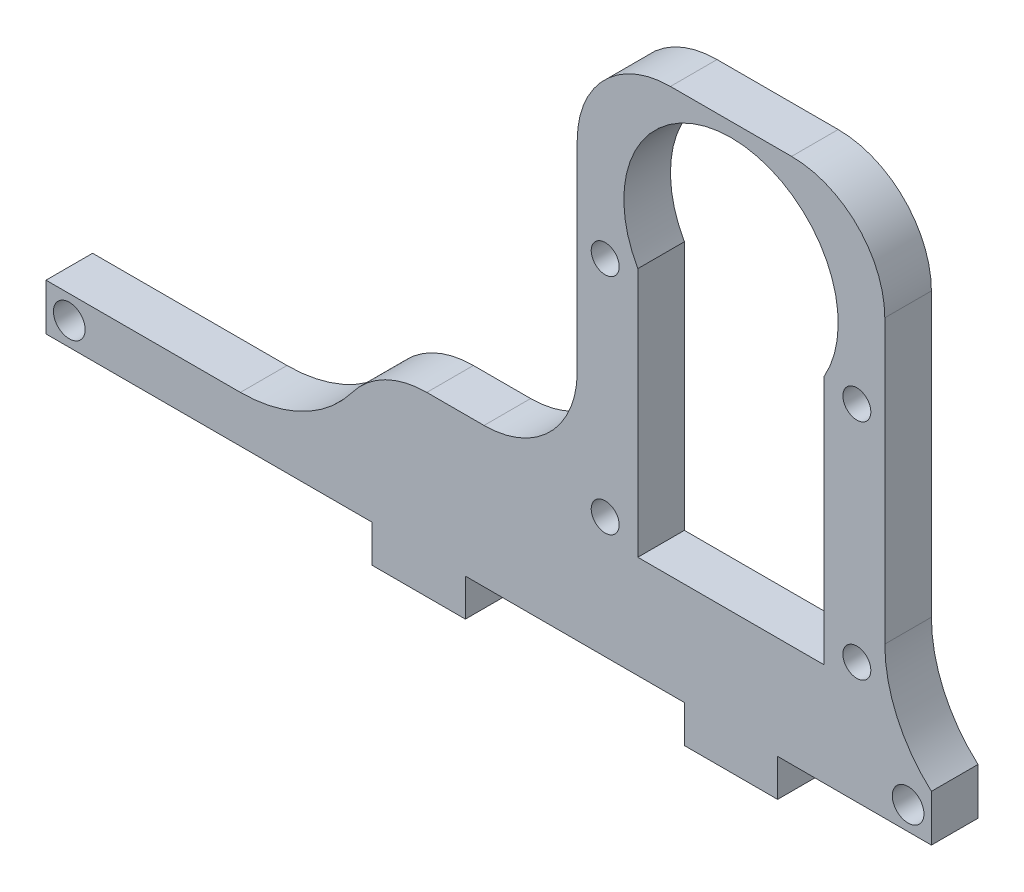
SolidWorks part; units mm, degrees
note: The reader was unsure of these and kept them because the rebuilt part matched: thickness of "Base-Flange1", "Sheet-Metal1".
ref_plane "Front Plane" through (0, 0, 0) normal (0, 0, 1) x (1, 0, 0)
ref_plane "Top Plane" through (0, 0, 0) normal (0, 1, 0) x (1, 0, 0)
ref_plane "Right Plane" through (0, 0, 0) normal (1, 0, 0) x (0, 0, -1)
sketch "Sketch2" plane through (0, 0, 0) normal (0, 0, 1) x (1, 0, 0)
  line L0 (-13.5, -30.5) -> (-13.5, -6.5) construction
  line L1 (-6.5, 13) -> (6.5, 13)
  line L3 (-28.5, -43.5) -> (-5, -43.5)
  line L4 (16.5, 3) -> (16.5, -38.5)
  line L5 (-10, -5.6789) -> (10, -5.6789) construction
  line L6 (-38.5, -43.5) -> (-28.5, -43.5) construction
  line L7 (-38.5, -43.5) -> (-28.5, -43.5) construction
  line L8 (-38.5, -43.5) -> (-38.5, -47.5)
  line L9 (-38.5, -47.5) -> (-28.5, -47.5)
  line L10 (-28.5, -43.5) -> (-28.5, -47.5)
  line L14 (-5, -43.5) -> (-5, -47.5)
  line L16 (-10, -5.6789) -> (-10, -32.5)
  line L21 (-10, -32.5) -> (10, -32.5)
  line L22 (10, -5.6789) -> (10, -32.5)
  line L23 (-13.5, -6.5) -> (13.5, -6.5) construction
  line L24 (-16.5, 3) -> (-16.5, -28.5)
  line L25 (-16.5, -28.5) -> (-38.5, -28.5)
  line L26 (-38.5, -28.5) -> (-38.5, -38.5)
  line L27 (-5, -47.5) -> (5, -47.5)
  line L28 (5, -43.5) -> (16.5, -43.5)
  line L29 (5, -47.5) -> (5, -43.5)
  line L30 (16.5, -38.5) -> (16.5, -43.5) construction
  line L31 (16.5, -43.5) -> (21.5, -43.5)
  line L32 (16.5, -43.5) -> (16.5, -38.5) construction
  line L33 (16.5, -38.5) -> (21.5, -38.5)
  line L34 (21.5, -43.5) -> (21.5, -38.5)
  line L35 (-38.5, -38.5) -> (-38.5, -43.5) construction
  line L36 (-38.5, -43.5) -> (-73.5, -43.5)
  line L37 (-38.5, -43.5) -> (-38.5, -38.5) construction
  line L38 (-38.5, -38.5) -> (-73.5, -38.5)
  line L39 (-73.5, -43.5) -> (-73.5, -38.5)
  arc A6 (6.5, 13) -> (16.5, 3) centre (6.5, 3) cw
  arc A7 (-6.5, 13) -> (-16.5, 3) centre (-6.5, 3) ccw
  arc A12 (10, -5.6789) -> (-10, -5.6789) centre (0, 0) ccw
  circle A13 centre (-13.5, -6.5) radius 1.5
  circle A14 centre (-13.5, -30.5) radius 1.5
  circle A15 centre (13.5, -6.5) radius 1.5
  circle A16 centre (13.5, -30.5) radius 1.5
  arc A17 (-10, -5.6789) -> (-9.4868, -6.5) centre (0, 0) ccw construction
  arc A18 (-9.4868, -6.5) -> (9.4868, -6.5) centre (0, 0) ccw construction
  arc A19 (9.4868, -6.5) -> (10, -5.6789) centre (0, 0) ccw construction
  circle A20 centre (19, -41) radius 1.7
  circle A21 centre (-71, -41) radius 1.7
  point P29 (0, -6.5)
  point P31 (0, 13)
  point P32 (0, -32.5)
  point P35 (0, -47.5)
  point P43 (21.5, -41)
  point P45 (19, -43.5)
  point P50 (-73.5, -41)
  dimension "D2" = 23
  dimension "D3" = 32.5
  dimension "D4" = 20
  dimension "D12" = 10
  dimension "D13" = 10
  dimension "D18" = 5
  dimension "D6" = 3
  dimension "D11" = 13
  dimension "D20" = 3.4
  dimension "D23" = 3.4
  dimension "D5" = 43.5
  dimension "D7" = 27
  dimension "D8" = 24
  dimension "D9" = 6.5
  dimension "D10" = 3
  dimension "D14" = 10
  dimension "D15" = 4
  dimension "D16" = 15
  dimension "D17" = 55
  dimension "D19" = 5
  dimension "D21" = 71
  dimension "D22" = 2.5
base flange "Base-Flange1" sketch "Sketch2" thickness 5 reverse thickness direction no parameters "D1"=0.7366
fillet "Fillet1" radius 15 2 edges at (-38.5, -38.5, -2.5) (16.5, -38.5, -2.5)
fillet "Fillet2" radius 10 2 edges at (-16.5, -28.5, -2.5) (-38.5, -28.5, -2.5)
sketch "Bend-Lines1" [suppressed] plane through (0, 0, 0) normal (0, 1, 0) x (1, 0, 0)
sketch "Bounding-Box1" [suppressed] plane through (0, 0, 0) normal (0, 1, 0) x (1, 0, 0)
sheet metal parameters "Sheet-Metal1" thickness 5 parameters "D1"=0.7366
flat pattern "Flat-Pattern1" [suppressed]
sketch "Bend-Lines2" plane through (0, 0, 0) normal (0, 1, 0) x (1, 0, 0)
sketch3d "Bounding-Box2" [suppressed]
  line L0 (-75, -50.5, 0) -> (15, -50.5, 0) construction
  line L1 (-75, 10, 0) -> (15, 10, 0) construction
  line L2 (-75, -50.5, 0) -> (-75, 10, 0) construction
  line L3 (15, -50.5, 0) -> (15, 10, 0) construction
